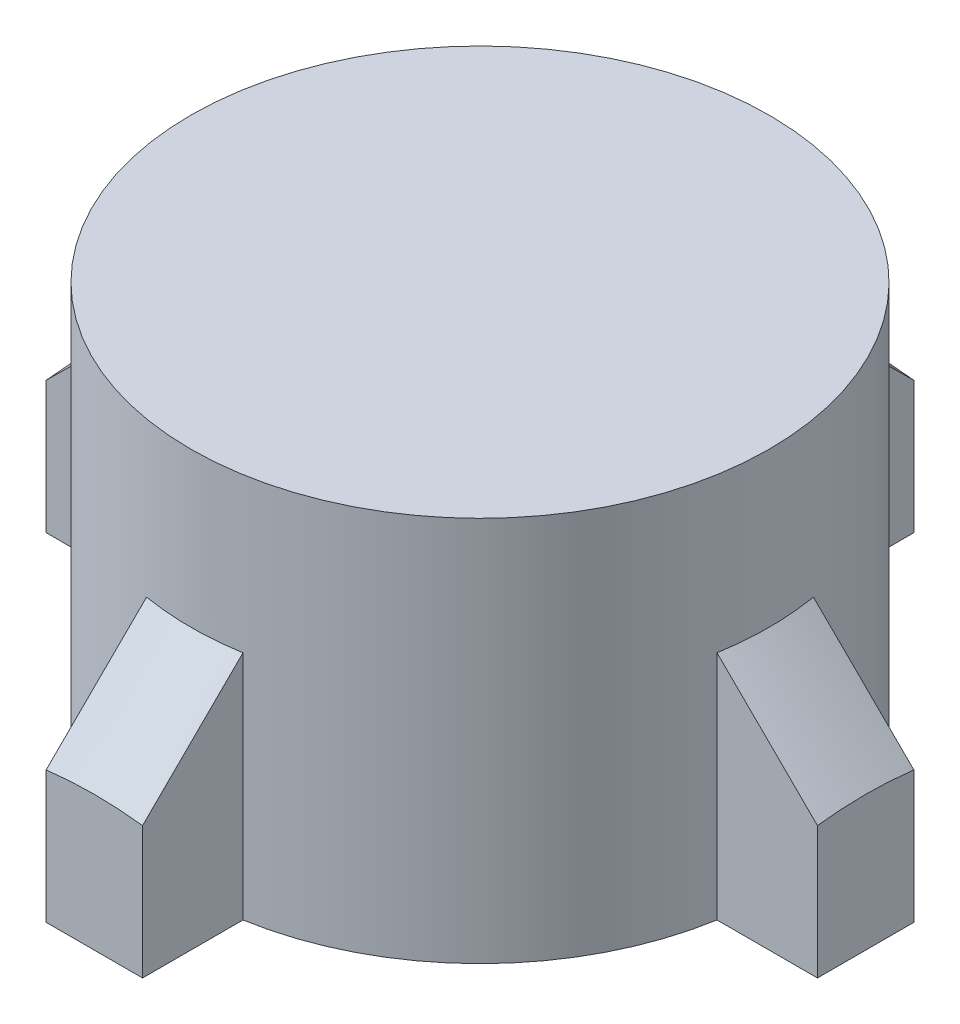
SolidWorks part; units mm, degrees
ref_plane "Front Plane" through (0, 0, 0) normal (0, 0, 1) x (1, 0, 0)
ref_plane "Top Plane" through (0, 0, 0) normal (0, 1, 0) x (1, 0, 0)
ref_plane "Right Plane" through (0, 0, 0) normal (1, 0, 0) x (0, 0, -1)
sketch "Sketch1" plane through (0, 0, 0) normal (0, 1, 0) x (1, 0, 0)
  circle A0 centre (0, 0) radius 75
  dimension "D1" = 150
extrude "Boss-Extrude1" add sketch "Sketch1" along normal blind 100
sketch "Sketch2" plane through (0, 0, 0) normal (0, -1, 0) x (1, 0, 0)
  line L1 (-100, -12.5) -> (100, -12.5)
  line L2 (-100, -12.5) -> (-100, 12.5)
  line L3 (-100, 12.5) -> (100, 12.5)
  line L4 (100, -12.5) -> (100, 12.5)
  line L5 (-100, -12.5) -> (100, 12.5) construction
  line L6 (-100, 12.5) -> (100, -12.5) construction
  line L7 (-12.5, -100) -> (12.5, -100)
  line L8 (-12.5, -100) -> (-12.5, 100)
  line L9 (-12.5, 100) -> (12.5, 100)
  line L10 (12.5, -100) -> (12.5, 100)
  line L11 (-12.5, -100) -> (12.5, 100) construction
  line L12 (-12.5, 100) -> (12.5, -100) construction
  point P0 (0, 0)
  point P5 (0, 0)
  circle M5 centre (0, 0) radius 75
  dimension "D1" = 25
  dimension "D2" = 200
extrude "Boss-Extrude2" add sketch "Sketch2" against normal blind 10 contours L3 L2 L1 M5 | L1 L4 L3 M5 | L10 L9 L8 M5 | L7 L10 L8 M5 region at (-87.3237, 0, 0) region at (0, 0, -87.3237) region at (0, 0, 87.3237) region at (87.3237, 0, 0)
chamfer "Chamfer1" distance 50 angle 45 4 edges at (0, 10, -75) (75, 10, 0) (0, 10, 75) (-75, 10, 0)
